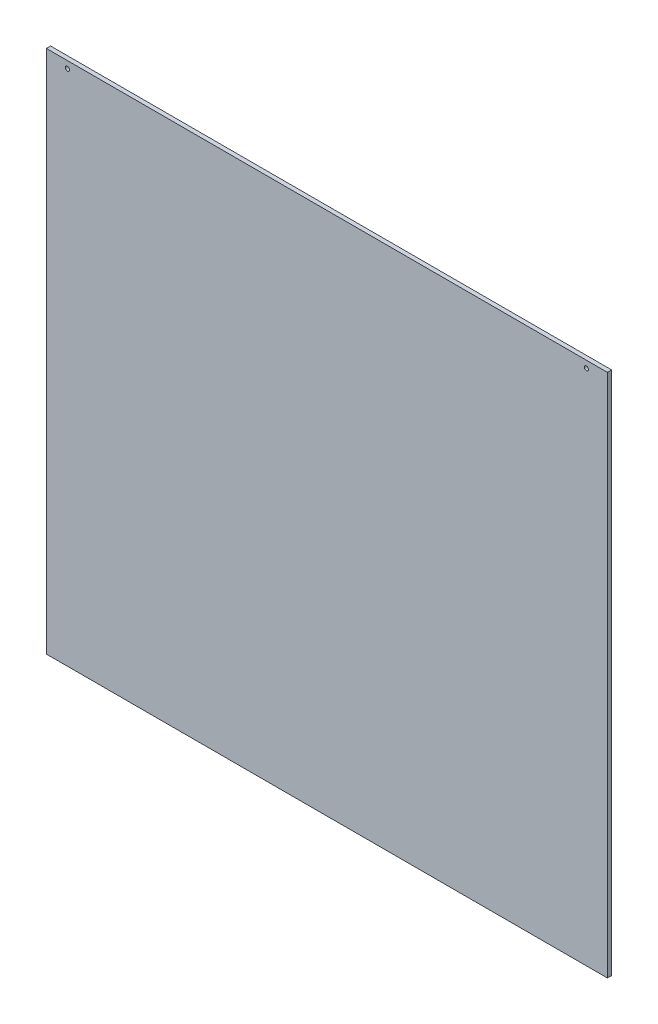
SolidWorks part; units mm, degrees
material "Acrylic (Medium-high impact)"
ref_plane "Front Plane" through (0, 0, 0) normal (0, 0, 1) x (1, 0, 0)
ref_plane "Top Plane" through (0, 0, 0) normal (0, 1, 0) x (1, 0, 0)
ref_plane "Right Plane" through (0, 0, 0) normal (1, 0, 0) x (0, 0, -1)
sketch "Sketch1" plane through (0, 0, 0) normal (0, 0, 1) x (1, 0, 0)
  line L1 (-200, -187) -> (200, -187)
  line L2 (-200, -187) -> (-200, 187)
  line L3 (-200, 187) -> (200, 187)
  line L4 (200, -187) -> (200, 187)
  line L5 (-200, -187) -> (200, 187) construction
  line L6 (-200, 187) -> (200, -187) construction
  point P0 (0, 0)
  dimension "D1" = 400
  dimension "D2" = 374
extrude "Boss-Extrude1" add sketch "Sketch1" along normal blind 3
sketch "Sketch2" plane through (0, 0, 0) normal (0, 0, -1) x (-1, 0, 0)
  line L0 (-1098.6774, 187) -> (48901.3226, 187) construction
  line L4 (-1000, 0) -> (49000, 0) construction
  line L6 (0, -1000) -> (0, 49000) construction
  line L7 (-200, 187) -> (200, 187) construction
  line L8 (-1098.6774, 182) -> (48901.3226, 182) construction
  line L9 (200, 187) -> (200, -187) construction
  circle A4 centre (185, 182) radius 1.5
  circle A5 centre (-185, 182) radius 1.5
  dimension "D2" = 15
  dimension "D3" = 3
  dimension "D1" = 5
extrude "Cut-Extrude1" cut sketch "Sketch2" against normal up to next
